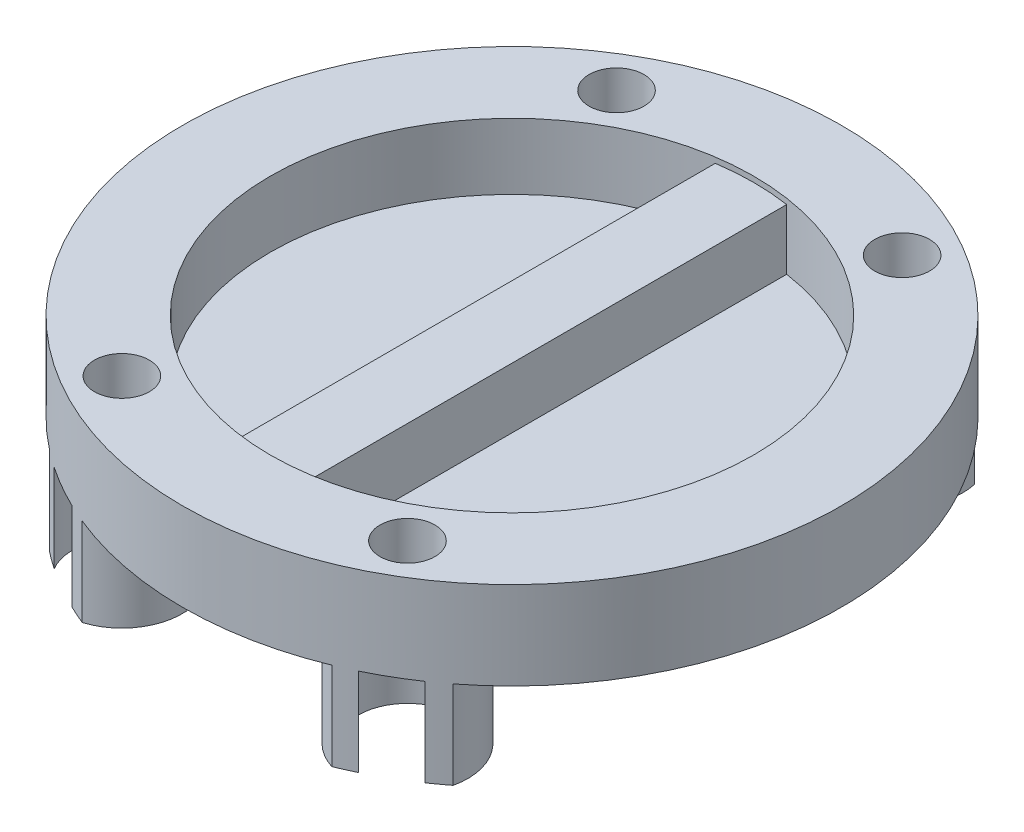
SolidWorks part; units mm, degrees
ref_plane "前基準面" through (0, 0, 0) normal (0, 0, 1) x (1, 0, 0)
ref_plane "上基準面" through (0, 0, 0) normal (0, 1, 0) x (1, 0, 0)
ref_plane "右基準面" through (0, 0, 0) normal (1, 0, 0) x (0, 0, -1)
sketch "草圖1" plane through (0, 0, 0) normal (0, 1, 0) x (1, 0, 0)
  line L0 (-24, 0) -> (24, 0) construction
  line L1 (-0.8, 19.31) -> (0.8, 19.31)
  line L2 (-0.8, 19.31) -> (-0.8, -19.31)
  line L3 (-0.8, -19.31) -> (0.8, -19.31)
  line L4 (0.8, 19.31) -> (0.8, -19.31)
  line L5 (-13.4, 12.7) -> (-11.8, 12.7)
  line L6 (-13.4, 12.7) -> (-13.4, -12.7)
  line L7 (-13.4, -12.7) -> (-11.8, -12.7)
  line L8 (-11.8, 12.7) -> (-11.8, -12.7)
  line L9 (0, 24) -> (0, -24) construction
  line L10 (13.4, -12.7) -> (11.8, -12.7)
  line L11 (11.8, 12.7) -> (11.8, -12.7)
  line L12 (13.4, 12.7) -> (11.8, 12.7)
  line L13 (13.4, 12.7) -> (13.4, -12.7)
  line L14 (13.4, 9.9287) -> (13.4, -10.0713)
  line L15 (-1, 19.6) -> (1, 19.6)
  line L16 (-1, 19.6) -> (-1, -19.6)
  line L17 (-1, -19.6) -> (1, -19.6)
  line L18 (1, 19.6) -> (1, -19.6)
  line L19 (-13.4, 5) -> (-16.4, 5)
  line L20 (-16.4, 5) -> (-16.4, -5)
  line L21 (-16.4, -5) -> (-13.4, -5)
  line L22 (-13.4, 5) -> (-13.4, -5)
  line L23 (0, 0) -> (-10.4, 18.0133) construction
  line L24 (9.8, 10) -> (11.8, 10)
  line L25 (9.8, 10) -> (9.8, -10)
  line L26 (9.8, -10) -> (11.8, -10)
  line L27 (11.8, 10) -> (11.8, -10)
  line L28 (0, 0) -> (10.4, 18.0133) construction
  line L29 (0, 0) -> (10.4, -18.0133) construction
  line L30 (0, 0) -> (-10.4, -18.0133) construction
  line L32 (-2.6, 21.2) -> (2.6, 21.2)
  line L33 (-2.6, 21.2) -> (-2.6, -21.2)
  line L34 (-2.6, -21.2) -> (2.6, -21.2)
  line L35 (2.6, 21.2) -> (2.6, -21.2)
  circle A0 centre (0, 0) radius 24
  circle A4 centre (-10.4, 18.0133) radius 3.2
  circle A9 centre (0, 0) radius 20.8
  arc A11 (-23.7808, 3.2365) -> (-23.7808, -3.2365) centre (0, 0) ccw
  arc A12 (-23.7808, 3.2365) -> (-23.7808, -3.2365) centre (0, 0) cw
  arc A13 (-9.0875, 22.213) -> (-14.6933, 18.9765) centre (0, 0) ccw
  arc A14 (-14.6933, 18.9765) -> (-9.0875, 22.213) centre (-10.4, 18.0133) ccw
  arc A15 (14.6933, 18.9765) -> (9.0875, 22.213) centre (0, 0) ccw
  arc A17 (23.7808, -3.2365) -> (23.7808, 3.2365) centre (0, 0) ccw
  arc A19 (9.0875, -22.213) -> (14.6933, -18.9765) centre (0, 0) ccw
  arc A25 (-13.5005, 19.8428) -> (-10.4341, 21.6132) centre (-10.4, 18.0133) ccw
  arc A26 (-10.4341, 21.6132) -> (-13.5005, 19.8428) centre (0, 0) ccw
  arc A30 (23.9346, -1.7704) -> (23.9346, 1.7704) centre (0, 0) ccw
  arc A32 (10.4341, -21.6132) -> (13.5005, -19.8428) centre (0, 0) ccw
  arc A34 (-13.5005, -19.8428) -> (-10.4341, -21.6132) centre (0, 0) ccw
  circle A35 centre (0, 0) radius 17.6
  arc A36 (-14.6933, -18.9765) -> (-9.0875, -22.213) centre (0, 0) ccw [skipped]
  arc A37 (14.6933, 18.9765) -> (9.0875, 22.213) centre (10.4, 18.0133) cw
  arc A38 (9.0875, 22.213) -> (14.6933, 18.9765) centre (0, 0) cw
  arc A39 (10.4341, 21.6132) -> (13.5005, 19.8428) centre (0, 0) cw
  arc A40 (13.5005, 19.8428) -> (10.4341, 21.6132) centre (10.4, 18.0133) cw
  circle A41 centre (10.4, 18.0133) radius 3.2
  arc A42 (13.5005, -19.8428) -> (10.4341, -21.6132) centre (10.4, -18.0133) ccw
  arc A43 (10.4341, -21.6132) -> (13.5005, -19.8428) centre (0, 0) ccw
  circle A44 centre (10.4, -18.0133) radius 3.2
  arc A45 (14.6933, -18.9765) -> (9.0875, -22.213) centre (10.4, -18.0133) ccw
  arc A46 (-14.6933, -18.9765) -> (-9.0875, -22.213) centre (-10.4, -18.0133) cw
  arc A47 (-9.0875, -22.213) -> (-14.6933, -18.9765) centre (0, 0) cw
  arc A48 (-10.4341, -21.6132) -> (-13.5005, -19.8428) centre (0, 0) cw
  arc A49 (-13.5005, -19.8428) -> (-10.4341, -21.6132) centre (-10.4, -18.0133) cw
  circle A50 centre (-10.4, -18.0133) radius 3.2
  circle A51 centre (-10.4, 18.0133) radius 2
  circle A52 centre (10.4, 18.0133) radius 2
  circle A53 centre (10.4, -18.0133) radius 2
  circle A54 centre (-10.4, -18.0133) radius 2
  point P39 (0, 0)
  point P56 (0, 0)
  point P74 (0, 0)
  dimension "D6" = 48
  dimension "D9" = 6.4
  dimension "D10" = 0.4
  dimension "D11" = 0.8
  dimension "D13" = 1.6
  dimension "D15" = 20
  dimension "D22" = 4
  dimension "D1" = 1.6
  dimension "D2" = 38.62
  dimension "D3" = 1.6
  dimension "D4" = 25.4
  dimension "D5" = 11
  dimension "D7" = 2
  dimension "D8" = 39.2
  dimension "D16" = 10
  dimension "D17" = 3
  dimension "D18" = 20
  dimension "D19" = 2
  dimension "D14" = 1.6
  dimension "D20" = 1.6
  dimension "D21" = 1.6
  dimension "D12" = 6
extrude "填料-伸長1" add sketch "草圖1" along normal blind 1.6 contours A35
extrude "填料-伸長2" add sketch "草圖1<4>" along normal blind 6 contours L34 L35 L32 L33
sketch "草圖1<4>" plane through (0, 0, 0) normal (0, 1, 0) x (1, 0, 0) same geometry as "草圖1"
extrude "填料-伸長3" add sketch "草圖1<7>" along normal blind 6.4 contours A35 | A0 | A51 | A52 | A54 | A53
sketch "草圖1<7>" plane through (0, 0, 0) normal (0, 1, 0) x (1, 0, 0) same geometry as "草圖1"
extrude "填料-伸長4" add sketch "草圖1<9>" against normal blind 6.4 contours A9 A49 A0 A46 | A35 A49 A9 A46 | A35 A49 A46 | A9 A49 A35 A46 | A12 A49 A9 A46 | A35 A45 A42 | A35 A45 A9 A42 | A9 A45 A12 A42 | A9 A45 A35 A42 | A12 A45 A9 A42 | A12 A40 A9 A37 | A9 A40 A12 A37 | A35 A40 A9 A37 | A35 A40 A37 | A9 A40 A35 A37 | A25 A13 A14 A9 | A14 A35 A25 | A35 A25 A9 A14 | A35 A14 A9 A25 | A25 A9 A14 A12 region at (-6.5422, 0, -17.9316) region at (-8.4966, 0, -14.7165) region at (6.5422, 0, -17.9316) region at (8.4966, 0, -14.7165) region at (-6.5422, 0, 17.9316) region at (-8.4966, 0, 14.7165) region at (-8.0604, 0, -21.0486) region at (-12.2581, 0, -14.6315) region at (8.4966, 0, 14.7165) region at (6.5422, 0, 17.9316) region at (8.0604, 0, -21.0486) region at (12.2581, 0, -14.6315) region at (-8.0604, 0, 21.0486) region at (-12.2581, 0, 14.6315) region at (-14.1984, 0, -17.5048) region at (8.0604, 0, 21.0486) region at (12.2581, 0, 14.6315) region at (14.1984, 0, -17.5048) region at (-14.1984, 0, 17.5048) region at (14.1984, 0, 17.5048)
sketch "草圖1<9>" plane through (0, 0, 0) normal (0, 1, 0) x (1, 0, 0) same geometry as "草圖1"
extrude "除料-伸長1" cut sketch "草圖1<5>" along normal blind 2.8 contours L17 L18 L15 L16
sketch "草圖1<5>" plane through (0, 0, 0) normal (0, 1, 0) x (1, 0, 0) same geometry as "草圖1"
sketch "草圖2" plane through (0, 6.4, 0) normal (0, 1, 0) x (1, 0, 0)
  line L0 (13.4, 9.9287) -> (13.4, -10.0713) construction
  line L1 (13.4, -12.7) -> (11.8, -12.7) construction
  line L2 (11.8, 12.7) -> (11.8, -12.7) construction
  line L3 (13.4, 12.7) -> (11.8, 12.7) construction
  line L4 (13.4, 12.7) -> (13.4, -12.7) construction
  line L5 (-13.4, 12.7) -> (-11.8, 12.7) construction
  line L6 (-11.8, 12.7) -> (-11.8, -12.7) construction
  line L7 (-13.4, -12.7) -> (-11.8, -12.7) construction
  line L8 (-13.4, 12.7) -> (-13.4, -12.7) construction
  line L9 (-0.8, 19.31) -> (0.8, 19.31) construction
  line L10 (0.8, 19.31) -> (0.8, -19.31) construction
  line L11 (-0.8, -19.31) -> (0.8, -19.31) construction
  line L12 (-0.8, 19.31) -> (-0.8, -19.31) construction
  line L13 (-1, 19.6) -> (1, 19.6) construction
  line L14 (1, 19.6) -> (1, -19.6) construction
  line L15 (-1, -19.6) -> (1, -19.6) construction
  line L16 (-1, 19.6) -> (-1, -19.6) construction
  line L17 (-2.6, 21.2) -> (2.6, 21.2) construction
  line L18 (-2.6, 21.2) -> (-2.6, -21.2) construction
  line L19 (-2.6, -21.2) -> (2.6, -21.2) construction
  line L20 (2.6, 21.2) -> (2.6, -21.2) construction
  line L21 (-13.4, 5) -> (-16.4, 5) construction
  line L22 (-16.4, 5) -> (-16.4, -5) construction
  line L23 (-16.4, -5) -> (-13.4, -5) construction
  line L24 (-13.4, 5) -> (-13.4, -5) construction
  line L25 (9.8, 10) -> (11.8, 10) construction
  line L26 (11.8, 10) -> (11.8, -10) construction
  line L27 (9.8, -10) -> (11.8, -10) construction
  line L28 (9.8, 10) -> (9.8, -10) construction
  line L29 (13.4, 9.9287) -> (13.4, -10.0713)
  line L30 (13.4, -12.7) -> (11.8, -12.7)
  line L31 (11.8, 12.7) -> (11.8, -12.7)
  line L32 (13.4, 12.7) -> (11.8, 12.7)
  line L33 (13.4, 12.7) -> (13.4, -12.7)
  line L34 (-13.4, 12.7) -> (-11.8, 12.7)
  line L35 (-11.8, 12.7) -> (-11.8, -12.7)
  line L36 (-13.4, -12.7) -> (-11.8, -12.7)
  line L37 (-13.4, 12.7) -> (-13.4, -12.7)
  line L38 (-0.8, 19.31) -> (0.8, 19.31)
  line L39 (0.8, 19.31) -> (0.8, -19.31)
  line L40 (-0.8, -19.31) -> (0.8, -19.31)
  line L41 (-0.8, 19.31) -> (-0.8, -19.31)
  line L42 (-1, 19.6) -> (1, 19.6)
  line L43 (1, 19.6) -> (1, -19.6)
  line L44 (-1, -19.6) -> (1, -19.6)
  line L45 (-1, 19.6) -> (-1, -19.6)
  line L46 (-2.6, 21.2) -> (2.6, 21.2)
  line L47 (-2.6, 21.2) -> (-2.6, -21.2)
  line L48 (-2.6, -21.2) -> (2.6, -21.2)
  line L49 (2.6, 21.2) -> (2.6, -21.2)
  line L50 (-13.4, 5) -> (-16.4, 5)
  line L51 (-16.4, 5) -> (-16.4, -5)
  line L52 (-16.4, -5) -> (-13.4, -5)
  line L53 (-13.4, 5) -> (-13.4, -5)
  line L54 (9.8, 10) -> (11.8, 10)
  line L55 (11.8, 10) -> (11.8, -10)
  line L56 (9.8, -10) -> (11.8, -10)
  line L57 (9.8, 10) -> (9.8, -10)
  arc A0 (14.6933, 18.9765) -> (9.0875, 22.213) centre (0, 0) ccw construction
  circle A1 centre (0, 0) radius 24
  circle A2 centre (0, 0) radius 24
  arc A3 (9.0875, 22.213) -> (14.6933, 18.9765) centre (10.4, 18.0133) ccw construction
  arc A4 (14.6933, 18.9765) -> (9.0875, 22.213) centre (0, 0) ccw construction
  arc A5 (23.7808, -3.2365) -> (23.7808, 3.2365) centre (0, 0) ccw construction
  arc A6 (-13.5005, -19.8428) -> (-10.4341, -21.6132) centre (0, 0) ccw construction
  arc A7 (-13.5005, -19.8428) -> (-10.4341, -21.6132) centre (0, 0) ccw construction
  arc A8 (-10.4341, -21.6132) -> (-13.5005, -19.8428) centre (-10.4, -18.0133) ccw construction
  arc A9 (10.4341, -21.6132) -> (13.5005, -19.8428) centre (0, 0) ccw construction
  arc A10 (13.5005, -19.8428) -> (10.4341, -21.6132) centre (10.4, -18.0133) ccw construction
  arc A11 (10.4341, -21.6132) -> (13.5005, -19.8428) centre (0, 0) ccw construction
  arc A12 (23.9346, -1.7704) -> (23.9346, 1.7704) centre (0, 0) ccw construction
  arc A13 (-23.7808, 3.2365) -> (-23.7808, -3.2365) centre (0, 0) ccw construction
  arc A14 (-23.7808, -3.2365) -> (-23.7808, 3.2365) centre (0, 0) ccw construction
  circle A15 centre (0, 0) radius 20.8 construction
  circle A16 centre (-10.4, 18.0133) radius 3.2 construction
  circle A17 centre (0, 0) radius 24 construction
  circle A18 centre (10.4, -18.0133) radius 3.2 construction
  circle A19 centre (10.4, 18.0133) radius 3.2 construction
  arc A20 (13.5005, 19.8428) -> (10.4341, 21.6132) centre (0, 0) ccw construction
  arc A21 (10.4341, 21.6132) -> (13.5005, 19.8428) centre (10.4, 18.0133) ccw construction
  circle A22 centre (0, 0) radius 17.6 construction
  arc A23 (-9.0875, 22.213) -> (-14.6933, 18.9765) centre (0, 0) ccw construction
  arc A24 (-14.6933, 18.9765) -> (-9.0875, 22.213) centre (-10.4, 18.0133) ccw construction
  circle A25 centre (-10.4, -18.0133) radius 2 construction
  circle A26 centre (10.4, -18.0133) radius 2 construction
  circle A27 centre (10.4, 18.0133) radius 2 construction
  circle A28 centre (-10.4, 18.0133) radius 2 construction
  circle A29 centre (-10.4, -18.0133) radius 3.2 construction
  arc A30 (-9.0875, -22.213) -> (-14.6933, -18.9765) centre (-10.4, -18.0133) ccw construction
  arc A31 (-14.6933, -18.9765) -> (-9.0875, -22.213) centre (0, 0) ccw construction
  arc A32 (-13.5005, 19.8428) -> (-10.4341, 21.6132) centre (-10.4, 18.0133) ccw construction
  arc A33 (-10.4341, 21.6132) -> (-13.5005, 19.8428) centre (0, 0) ccw construction
  arc A34 (9.0875, -22.213) -> (14.6933, -18.9765) centre (0, 0) ccw construction
  arc A35 (14.6933, -18.9765) -> (9.0875, -22.213) centre (10.4, -18.0133) ccw construction
  arc A36 (14.6933, 18.9765) -> (9.0875, 22.213) centre (0, 0) ccw
  arc A37 (9.0875, 22.213) -> (14.6933, 18.9765) centre (10.4, 18.0133) ccw
  arc A38 (14.6933, 18.9765) -> (9.0875, 22.213) centre (0, 0) ccw
  arc A39 (23.7808, -3.2365) -> (23.7808, 3.2365) centre (0, 0) ccw
  arc A40 (-13.5005, -19.8428) -> (-10.4341, -21.6132) centre (0, 0) ccw
  arc A41 (-13.5005, -19.8428) -> (-10.4341, -21.6132) centre (0, 0) ccw
  arc A42 (-10.4341, -21.6132) -> (-13.5005, -19.8428) centre (-10.4, -18.0133) ccw
  arc A43 (10.4341, -21.6132) -> (13.5005, -19.8428) centre (0, 0) ccw
  arc A44 (13.5005, -19.8428) -> (10.4341, -21.6132) centre (10.4, -18.0133) ccw
  arc A45 (10.4341, -21.6132) -> (13.5005, -19.8428) centre (0, 0) ccw
  arc A46 (23.9346, -1.7704) -> (23.9346, 1.7704) centre (0, 0) ccw
  arc A47 (-23.7808, 3.2365) -> (-23.7808, -3.2365) centre (0, 0) ccw
  arc A48 (-23.7808, -3.2365) -> (-23.7808, 3.2365) centre (0, 0) ccw
  circle A49 centre (0, 0) radius 20.8
  circle A50 centre (-10.4, 18.0133) radius 3.2
  circle A51 centre (0, 0) radius 24
  circle A52 centre (10.4, -18.0133) radius 3.2
  circle A53 centre (10.4, 18.0133) radius 3.2
  arc A54 (13.5005, 19.8428) -> (10.4341, 21.6132) centre (0, 0) ccw
  arc A55 (10.4341, 21.6132) -> (13.5005, 19.8428) centre (10.4, 18.0133) ccw
  circle A56 centre (0, 0) radius 17.6
  arc A57 (-9.0875, 22.213) -> (-14.6933, 18.9765) centre (0, 0) ccw
  arc A58 (-14.6933, 18.9765) -> (-9.0875, 22.213) centre (-10.4, 18.0133) ccw
  circle A59 centre (-10.4, -18.0133) radius 2
  circle A60 centre (10.4, -18.0133) radius 2
  circle A61 centre (10.4, 18.0133) radius 2
  circle A62 centre (-10.4, 18.0133) radius 2
  circle A63 centre (-10.4, -18.0133) radius 3.2
  arc A64 (-9.0875, -22.213) -> (-14.6933, -18.9765) centre (-10.4, -18.0133) ccw
  arc A65 (-14.6933, -18.9765) -> (-9.0875, -22.213) centre (0, 0) ccw
  arc A66 (-13.5005, 19.8428) -> (-10.4341, 21.6132) centre (-10.4, 18.0133) ccw
  arc A67 (-10.4341, 21.6132) -> (-13.5005, 19.8428) centre (0, 0) ccw
  arc A68 (9.0875, -22.213) -> (14.6933, -18.9765) centre (0, 0) ccw
  arc A69 (14.6933, -18.9765) -> (9.0875, -22.213) centre (10.4, -18.0133) ccw
  dimension "D1" = 0
